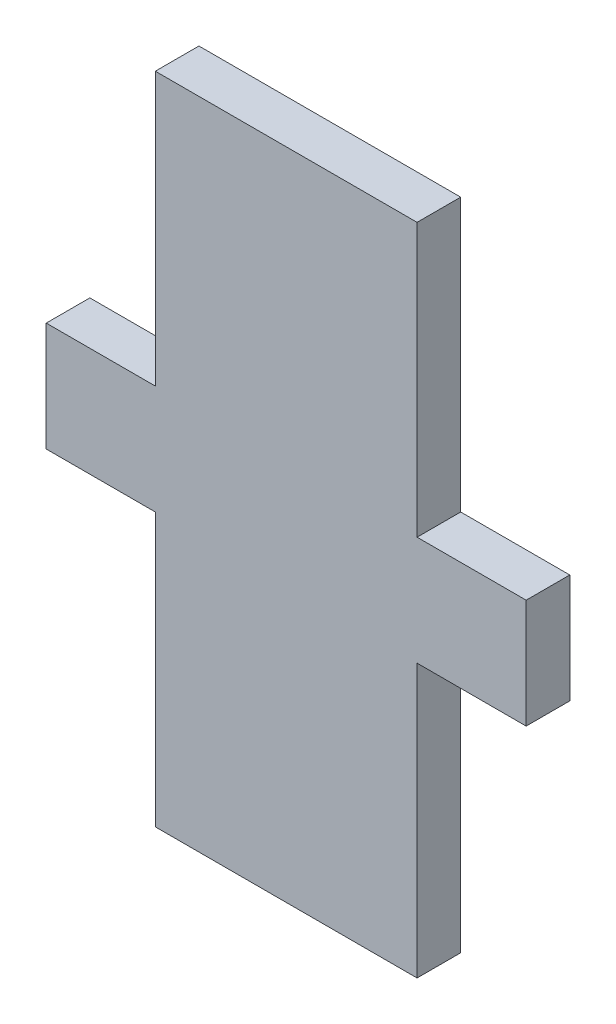
SolidWorks part; units mm, degrees
ref_plane "Front Plane" through (0, 0, 0) normal (0, 0, 1) x (1, 0, 0)
ref_plane "Top Plane" through (0, 0, 0) normal (0, 1, 0) x (1, 0, 0)
ref_plane "Right Plane" through (0, 0, 0) normal (1, 0, 0) x (0, 0, -1)
sketch "Sketch1" plane through (0, 0, 0) normal (0, 0, 1) x (1, 0, 0)
  line L1 (-30, 75) -> (30, 75)
  line L2 (-30, 75) -> (-30, -75)
  line L3 (-30, -75) -> (30, -75)
  line L4 (30, 75) -> (30, -75)
  line L5 (-30, 75) -> (30, -75) construction
  line L6 (-30, -75) -> (30, 75) construction
  point P0 (0, 0)
  dimension "D1" = 30
  dimension "D2" = 75
extrude "Boss-Extrude1" add sketch "Sketch1" against normal blind 10
sketch "Sketch2" plane through (0, 0, 0) normal (0, 0, 1) x (1, 0, 0)
  line L0 (-30, 12.5) -> (-30, -12.5)
  line L2 (30, -75) -> (30, 75) construction
  line L3 (30, 12.5) -> (30, -12.5)
  line L4 (55, 0) -> (55, 12.5)
  line L5 (55, 0) -> (55, -12.5)
  line L6 (55, -12.5) -> (30, -12.5)
  line L7 (55, 12.5) -> (30, 12.5)
  line L11 (-55, 12.5) -> (-30, 12.5)
  line L12 (-55, -12.5) -> (-30, -12.5)
  line L13 (-55, 0) -> (-55, -12.5)
  line L14 (-55, 0) -> (-55, 12.5)
extrude "Boss-Extrude2" add sketch "Sketch2" against normal blind 10
